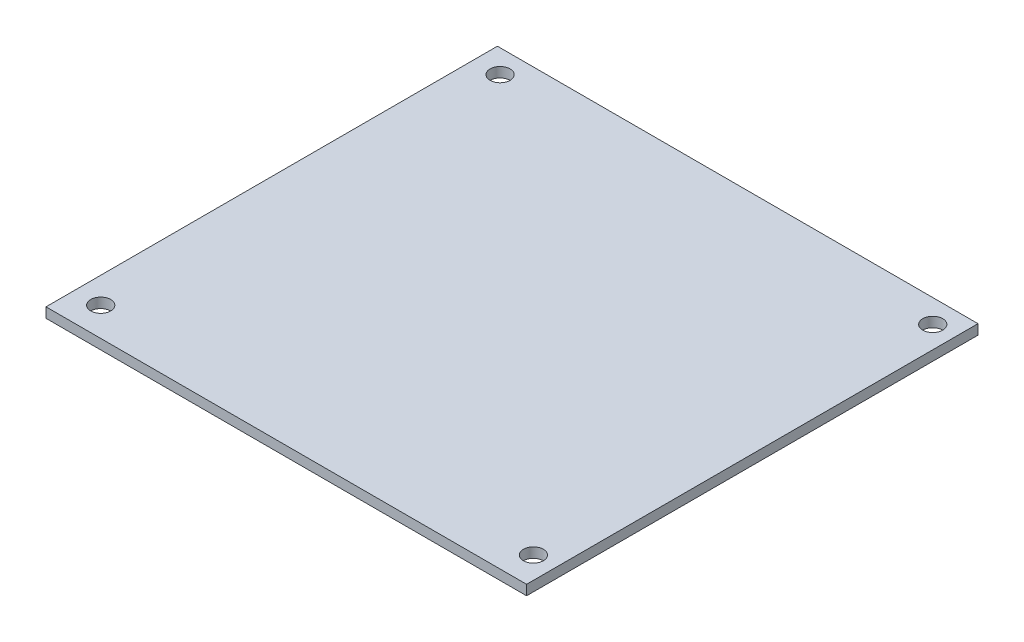
SolidWorks part; units mm, degrees
ref_plane "Plan de face" through (0, 0, 0) normal (0, 0, 1) x (1, 0, 0)
ref_plane "Plan de dessus" through (0, 0, 0) normal (0, 1, 0) x (1, 0, 0)
ref_plane "Plan de droite" through (0, 0, 0) normal (1, 0, 0) x (0, 0, -1)
sketch "Esquisse1" plane through (0, 0, 0) normal (0, 1, 0) x (1, 0, 0)
  line L1 (-36.1, 33.91) -> (36.1, 33.91)
  line L2 (-36.1, 33.91) -> (-36.1, -33.91)
  line L3 (-36.1, -33.91) -> (36.1, -33.91)
  line L4 (36.1, 33.91) -> (36.1, -33.91)
  line L5 (-36.1, 33.91) -> (36.1, -33.91) construction
  line L6 (-36.1, -33.91) -> (36.1, 33.91) construction
  line L11 (-30.3, -11.09) -> (29.7, -11.09)
  line L12 (-30.3, -11.09) -> (-30.3, 18.91)
  line L17 (-30.3, 18.91) -> (29.7, 18.91)
  line L18 (29.7, -11.09) -> (29.7, 18.91)
  circle A0 centre (-32.2, 30.41) radius 1.5
  circle A1 centre (32.8, 30.41) radius 1.5
  circle A2 centre (-32.2, -29.59) radius 1.5
  circle A3 centre (32.8, -29.59) radius 1.5
  point P0 (0, 0)
  point P14 (0, 0)
  point P21 (0, 0)
  dimension "D1" = 3
  dimension "D2" = 65
  dimension "D3" = 60
  dimension "D9" = 6.4
  dimension "D4" = 30
  dimension "D5" = 60
  dimension "D6" = 15
  dimension "D7" = 67.82
  dimension "D8" = 72.2
  dimension "D10" = 41.5
  dimension "D11" = 3.9
extrude "Boss.-Extru.1" add sketch "Esquisse1" along normal blind 1.5 contours L1 L4 L3 L2 | A1 | A0 | A2 | A3
extrude "Boss.-Extru.2" add sketch "Esquisse1<4>" along normal blind 1.5
sketch "Esquisse1<4>" plane through (0, 0, 0) normal (0, 1, 0) x (1, 0, 0) same geometry as "Esquisse1"
